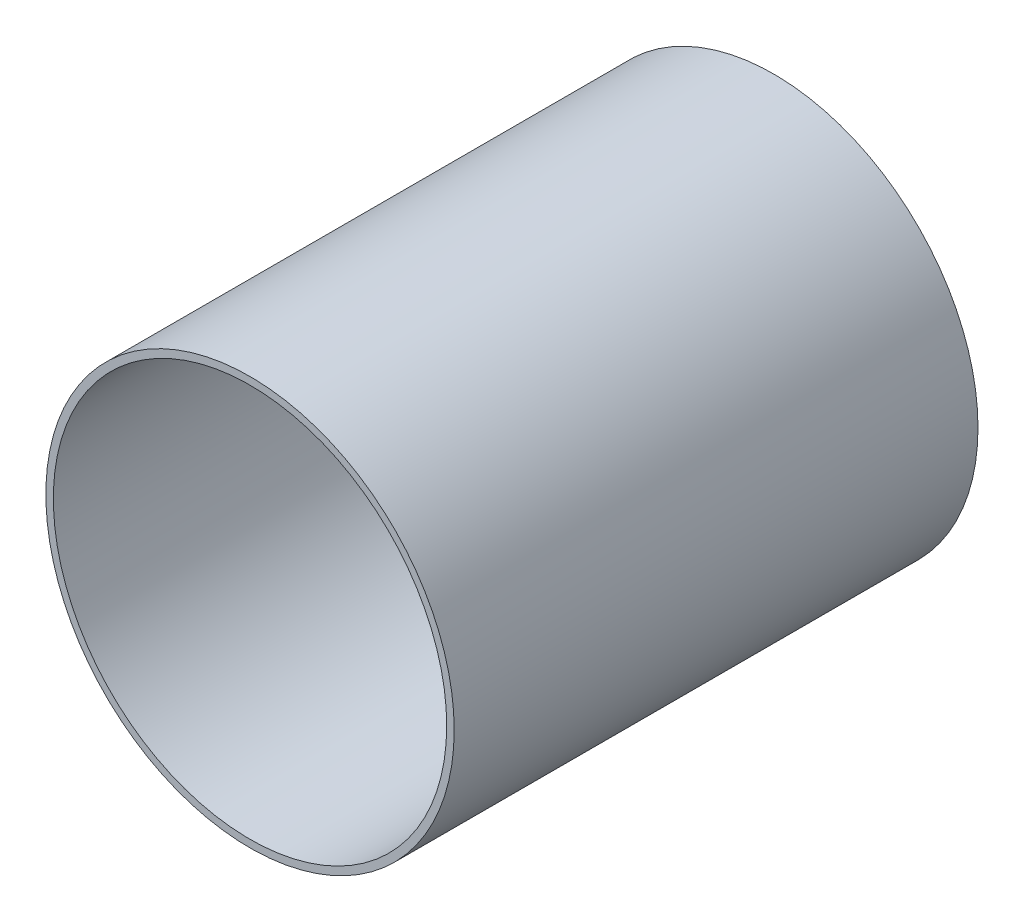
SolidWorks part; units mm, degrees
ref_plane "Front Plane" through (0, 0, 0) normal (0, 0, 1) x (1, 0, 0)
ref_plane "Top Plane" through (0, 0, 0) normal (0, 1, 0) x (1, 0, 0)
ref_plane "Right Plane" through (0, 0, 0) normal (1, 0, 0) x (0, 0, -1)
sketch "Sketch1" plane through (0, 0, 0) normal (0, 0, 1) x (1, 0, 0)
  circle A0 centre (0, 0) radius 49.5046
  circle A1 centre (0, 0) radius 47.6885
  dimension "D1" = 99.0092
  dimension "D2" = 95.377
extrude "Boss-Extrude1" add sketch "Sketch1" along normal blind 127
